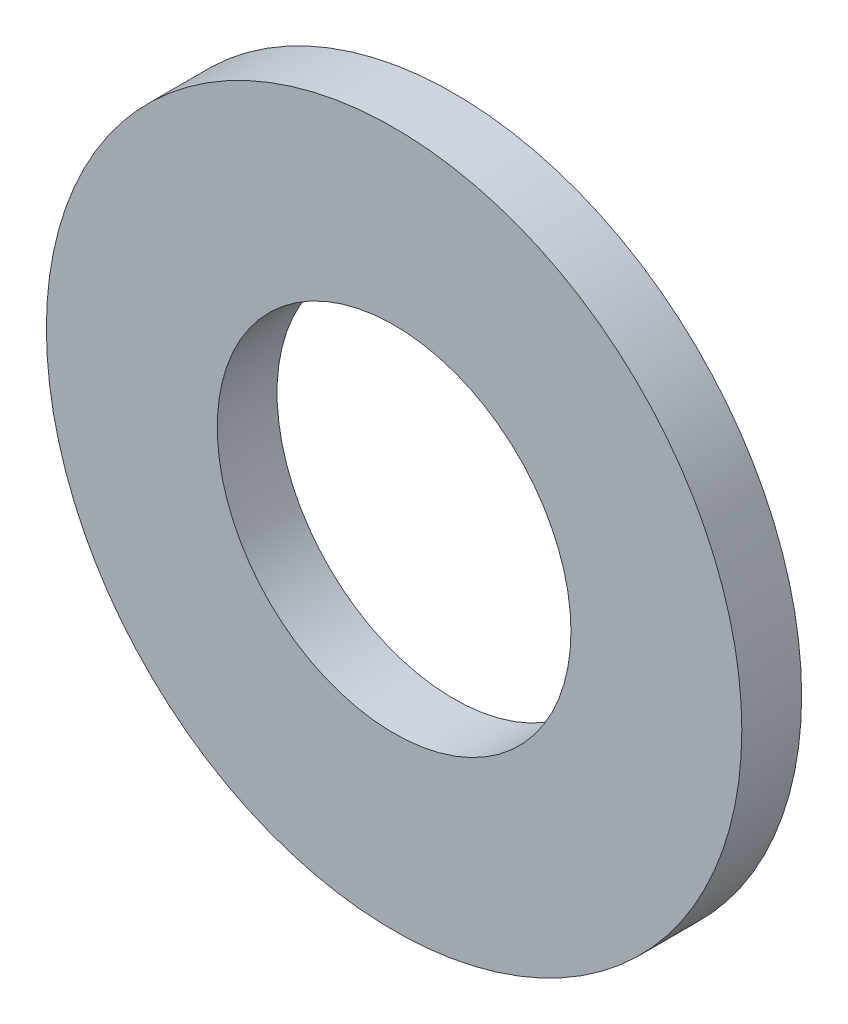
SolidWorks part; units mm, degrees
ref_plane "Plan de face" through (0, 0, 0) normal (0, 0, 1) x (1, 0, 0)
ref_plane "Plan de dessus" through (0, 0, 0) normal (0, 1, 0) x (1, 0, 0)
ref_plane "Plan de droite" through (0, 0, 0) normal (1, 0, 0) x (0, 0, -1)
sketch "Esquisse1" plane through (0, 0, 0) normal (0, 0, 1) x (1, 0, 0)
  circle A0 centre (0, 0) radius 10.35
  circle A1 centre (0, 0) radius 20.35
  dimension "D1" = 20.7
  dimension "D2" = 10
extrude "Boss.-Extru.1" add sketch "Esquisse1" along normal blind 3.5
